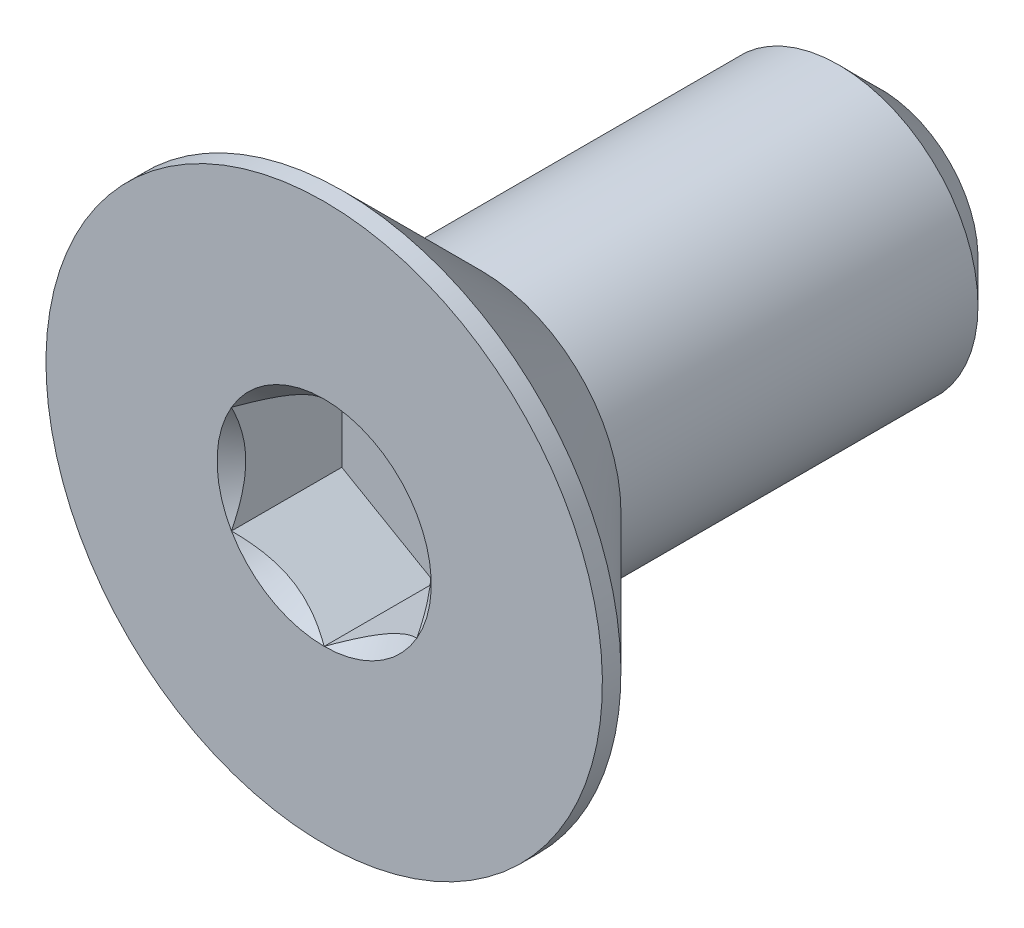
SolidWorks part; units mm, degrees
material "Alloy Steel"
ref_plane "Front" through (0, 0, 0) normal (0, 0, 1) x (1, 0, 0)
ref_plane "Top" through (0, 0, 0) normal (0, 1, 0) x (1, 0, 0)
ref_plane "Right" through (0, 0, 0) normal (1, 0, 0) x (0, 0, -1)
ref_axis "Central Axis" through (0, 0, -88.9324) along (0, 0, 1)
sketch "Sketch1" plane through (0, 0, 0) normal (1, 0, 0) x (0, 0, -1)
  line L0 (-3, 3) -> (-2.8, 3) construction
  line L1 (-2.8, 3) -> (-1.3, 1.5) construction
  line L2 (-3, 1.5) -> (3, 1.5) construction
  line L3 (3, 1.5) -> (3, 0) construction
  line L4 (3, 0) -> (-3, 0) construction
  line L5 (-3, 0) -> (-3, 3) construction
  line L6 (-3, 3) -> (-3, -3) construction
  line L7 (3, 1.5) -> (3, -1.5) construction
  line L8 (-3, -3) -> (-2.8, -3) construction
  line L9 (-2.8, -3) -> (-1.3, -1.5) construction
  line L11 (-3, 1.5) -> (-3, 0) construction
  line L12 (-1.3, 1.5) -> (-1.3, 0) construction
  line L13 (2.9687, 1.5541) -> (3.2188, 1.1211) construction
  line L14 (3.2188, 1.1211) -> (3.4687, 1.5541) construction
  line L15 (3.4687, 1.5541) -> (2.9687, 1.5541) construction
  line L16 (3.2188, 1.5541) -> (3.2188, 1.5) construction
  line L17 (3.2188, 1.5) -> (3.2188, 1.1752) construction
  line L18 (3.2188, 1.1752) -> (3.2188, 1.1211) construction
  line L19 (3.2188, 1.5271) -> (3.4531, 1.5271) construction
  line L20 (3.2188, 1.5271) -> (2.9844, 1.5271) construction
  line L21 (3, 1.5) -> (3.4375, 1.5) construction
  line L22 (3.1875, 1.1752) -> (3.25, 1.1752) construction
  line L23 (3, -1.5) -> (-1.3, -1.5) construction
  point P10 (1.75, -1.5)
  point P24 (-1.3, 1.5)
  point P30 (0, 0)
  dimension "Head Diameter" = 6
  dimension "Head Height" = 1.7
  dimension "Length" = 6
  dimension "Countersink Angle" = 90
  dimension "Thread Pitch" = 0.5
  dimension "D2" = 0.0625
  dimension "Minimum Thread Length" = 4.3
  dimension "Thread Size" = 3
  dimension "D1" = 1.25
sketch "Sketch2" plane through (0, 0, 0) normal (0, 0, 1) x (1, 0, 0)
  line L1 (0, 1.1547) -> (-1, 0.5774) construction
  line L2 (-1, 0.5774) -> (-1, -0.5774) construction
  line L3 (-1, -0.5774) -> (0, -1.1547) construction
  line L4 (0, -1.1547) -> (1, -0.5774) construction
  line L5 (1, -0.5774) -> (1, 0.5774) construction
  line L6 (1, 0.5774) -> (0, 1.1547) construction
  circle A0 centre (0, 0) radius 1 construction
  dimension "Drive Size" = 2
sketch "Sketch3" plane through (0, 0, 0) normal (1, 0, 0) x (0, 0, -1)
  line L0 (-3, 1.5) -> (3, 1.5)
  line L1 (3, 1.5) -> (3, 0)
  line L2 (3, 0) -> (-3, 0)
  line L3 (-3, 0) -> (-3, 1.5)
revolve "Revolve1" add sketch "Sketch3" angle 360 about L4
chamfer "Chamfer1" distance 0.45 angle 45 1 edges at (0, 1.5, -3)
sketch "Sketch6" plane through (0, 0, 0) normal (1, 0, 0) x (0, 0, -1)
  line L0 (-3, 3) -> (-2.8, 3)
  line L1 (-2.8, 3) -> (-1.3, 1.5)
  line L2 (-1.3, 1.5) -> (-1.3, 0)
  line L3 (-1.3, 0) -> (-3, 0)
  line L4 (-3, 0) -> (-3, 3)
revolve "Revolve2" add sketch "Sketch6" angle 360 about L4
sketch "Sketch8" plane through (0, 0, 3) normal (0, 0, 1) x (1, 0, 0)
  line L0 (0, 1.1547) -> (-1, 0.5774) construction
  line L1 (1, 0.5774) -> (0, 1.1547) construction
  line L2 (1, -0.5774) -> (1, 0.5774) construction
  line L3 (0, -1.1547) -> (1, -0.5774) construction
  line L4 (-1, 0.5774) -> (-1, -0.5774) construction
  line L5 (-1, -0.5774) -> (0, -1.1547) construction
  line L6 (0, 1.1547) -> (-1, 0.5774)
  line L7 (1, 0.5774) -> (0, 1.1547)
  line L8 (1, -0.5774) -> (1, 0.5774)
  line L9 (0, -1.1547) -> (1, -0.5774)
  line L10 (-1, 0.5774) -> (-1, -0.5774)
  line L11 (-1, -0.5774) -> (0, -1.1547)
extrude "Cut-Extrude1" cut sketch "Sketch8" against normal blind 1.19
sketch "Sketch9" plane through (0, 0, 3) normal (0, 0, 1) x (1, 0, 0)
  circle A0 centre (0, 0) radius 1.1547
extrude "Cut-Extrude2" cut sketch "Sketch9" against normal up to next (1.19 mm away) draft 45
ref_plane "Plane1" [suppressed] through (0, 0, 1.3) normal (0, 0, 1) x (1, 0, 0)
split "Split1" [suppressed] bodies to split 124
sketch "Sketch4" [suppressed] plane through (0, 0, -3) normal (0, 0, -1) x (-1, 0, 0)
  circle A0 centre (0, 0) radius 1.5 construction
  circle A1 centre (0, 0) radius 1.5
curve "Helix/Spiral1" [suppressed] pitch 0.5 height 4.8 turns 9.6
sketch "Sketch10" [suppressed] plane through (0, 0, 0) normal (1, 0, 0) x (0, 0, -1)
  line L0 (2.9844, 1.5271) -> (3.4531, 1.5271)
  line L1 (3.4531, 1.5271) -> (3.25, 1.1752)
  line L2 (3.25, 1.1752) -> (3.1875, 1.1752)
  line L3 (3.1875, 1.1752) -> (2.9844, 1.5271)
sweep "Cut-Sweep1" [suppressed] cut profiles "Sketch10" path "Helix/Spiral1"
equation "\"D2@Sketch1\" = \"Thread Pitch@Sketch1\" / 8"
equation "\"D4@Helix/Spiral1\"=\"Thread Pitch@Sketch1\""
equation "\"D3@Helix/Spiral1\"=\"Minimum Thread Length@Sketch1\"+\"Thread Pitch@Sketch1\""
equation "\"D1@Chamfer1\"=\"Thread Size@Sketch1\"*.15"
equation "\"D1@Cut-Extrude1\"=\"Head Height@Sketch1\"*.7"
equation "\"D1@Sketch1\"=\"Thread Pitch@Sketch1\"*2.5"
